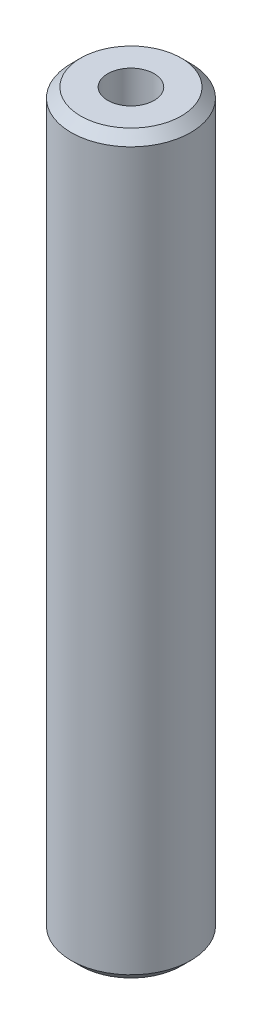
SolidWorks part; units mm, degrees
ref_plane "Front Plane" through (0, 0, 0) normal (0, 0, 1) x (1, 0, 0)
ref_plane "Top Plane" through (0, 0, 0) normal (0, 1, 0) x (1, 0, 0)
ref_plane "Right Plane" through (0, 0, 0) normal (1, 0, 0) x (0, 0, -1)
sketch "Sketch1" plane through (0, 0, 0) normal (0, 1, 0) x (1, 0, 0)
  circle A0 centre (0, 0) radius 12.5
  dimension "SHAFT_OD" = 25
extrude "Boss-Extrude1" add sketch "Sketch1" along normal blind 153.8618
sketch "Sketch2" plane through (0, 0, 0) normal (0, 1, 0) x (1, 0, 0)
  circle A0 centre (0, 0) radius 4.8506
  dimension "BORE_D" = 9.7012
extrude "Cut-Extrude1" cut sketch "Sketch2" along normal through all
chamfer "Chamfer1" distance 1.9914 angle 45 2 edges at (0, 153.8618, 12.5) (0, 0, 12.5)
